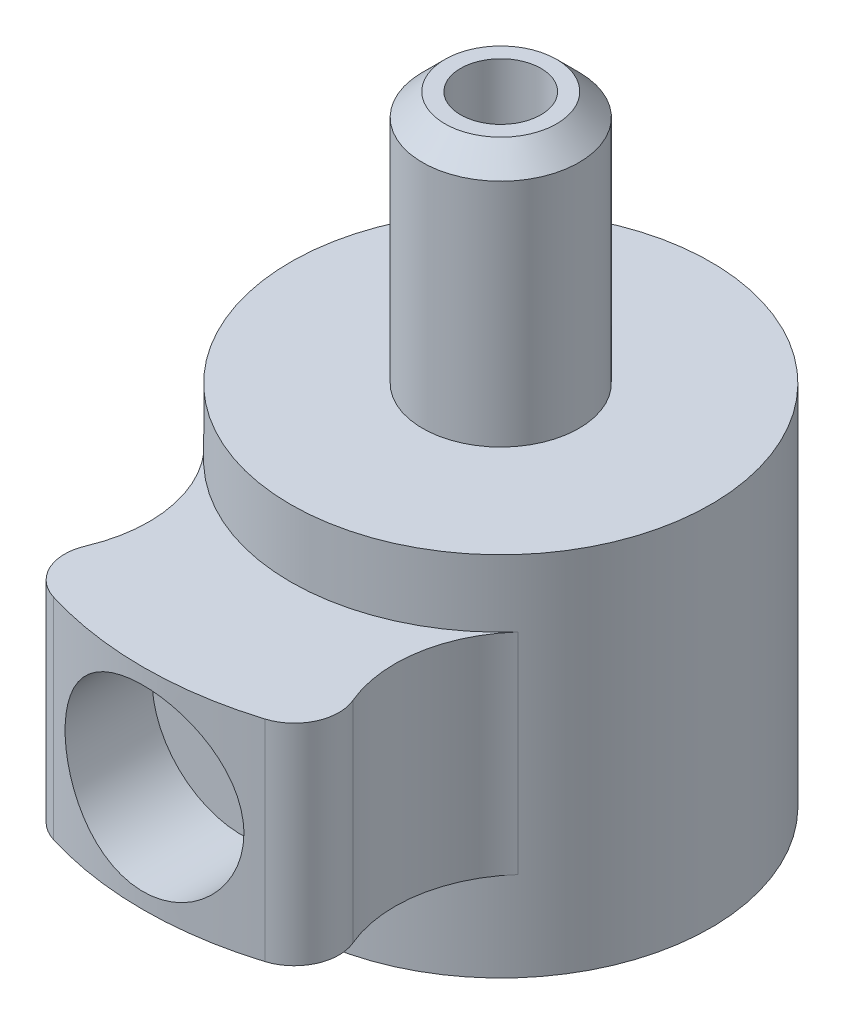
SolidWorks part; units mm, degrees
material "1060 Сплав"
ref_plane "Front Plane" through (0, 0, 0) normal (0, 0, 1) x (1, 0, 0)
ref_plane "Top Plane" through (0, 0, 0) normal (0, 1, 0) x (1, 0, 0)
ref_plane "Right Plane" through (0, 0, 0) normal (1, 0, 0) x (0, 0, -1)
sketch "Эскиз1" plane through (0, 0, 0) normal (1, 0, 0) x (0, 0, -1)
  line L0 (0, 0) -> (0, 10.689) construction
  line L1 (-3.4, 0) -> (-3.4, 6.5)
  line L2 (-3.4, 6.5) -> (-0.9, 6.5)
  line L3 (-0.9, 6.5) -> (-0.9, 13.85)
  line L4 (-0.9, 13.85) -> (-1.75, 13.85)
  line L5 (-1.75, 13.85) -> (-1.75, 8.2)
  line L6 (-1.75, 8.2) -> (-8, 8.2)
  line L7 (-8, 8.2) -> (-8, 0)
  line L8 (-8, 0) -> (-3.4, 0)
  line L9 (0, 0) -> (-3.4, 0) construction
  dimension "D1" = 6.8
  dimension "D2" = 1.8
  dimension "D3" = 3.5
  dimension "D4" = 16
  dimension "D5" = 8.2
  dimension "D6" = 13.85
  dimension "D7" = 6.5
revolve "Повернуть1" add sketch "Эскиз1" angle 360 about L0
sketch "Эскиз2" plane through (0, 8.2, 0) normal (0, 1, 0) x (1, 0, 0)
  line L0 (-5.75, -5.1213) -> (0, 0) construction
  line L1 (0, 0) -> (5.75, -5.1213) construction
  line L2 (-5.75, -5.1213) -> (5.75, -5.1213) construction
  line L3 (0, 0) -> (0, -5.1213) construction
  arc A0 (-5.75, -5.1213) -> (5.75, -5.1213) centre (0, 0) cw construction
  arc A1 (7.9903, -7.1166) -> (-7.9903, -7.1166) centre (0, 0) ccw
  arc A2 (3.5097, -3.126) -> (-3.5097, -3.126) centre (0, 0) ccw
  arc A3 (3.5097, -3.126) -> (7.9903, -7.1166) centre (5.75, -5.1213) ccw
  arc A4 (-7.9903, -7.1166) -> (-3.5097, -3.126) centre (-5.75, -5.1213) ccw
  point P4 (0, 7.7)
  dimension "D1" = 6
  dimension "D2" = 4.7
  dimension "D3" = 11.5
extrude "Вырез-Вытянуть1" cut sketch "Эскиз2" against normal through all
fillet "Скругление1" radius 1 2 edges at (3.5553, 4.1, 7.1666) (-3.5553, 4.1, 7.1666)
ref_plane "Плоскость1" through (0, 8.2, 8) normal (0, 0, 1) x (1, 0, 0)
sketch "Эскиз5" plane through (0, 8.2, 0) normal (0, 1, 0) x (1, 0, 0)
  circle A0 centre (0, 0) radius 4.7
extrude "Вырез-Вытянуть4" cut sketch "Эскиз5" against normal blind 1.5 flip side to cut
extrude "Вырез-Вытянуть5" cut sketch "Эскиз5<2>" along normal blind 2 from surface flip side to cut starting at face at (0, 0, -3.4)
sketch "Эскиз5<2>" plane through (0, 8.2, 0) normal (0, 1, 0) x (1, 0, 0) same geometry as "Эскиз5"
chamfer "Фаска1" distance 0.5 angle 45 1 edges at (0, 13.85, -1.75)
hole_wizard "M2 Tapped Hole1" positions "Sketch2" profile "Sketch3" tap size "M2" standard "ISO"
sketch "Sketch2" plane through (0, 8.2, 8) normal (0, 0, 1) x (1, 0, 0)
  line L0 (0, -3.85) -> (2.3648, -3.85)
  line L2 (2.3648, -6.2) -> (2.3648, -1.5) construction
  line L3 (0, -3.85) -> (0, -6.2)
  line L5 (-2.3648, -6.2) -> (2.3648, -6.2) construction
  point P0 (0, -3.85)
  point P8 (2.3648, -3.85)
  point P17 (0, -6.2)
sketch "Sketch3" plane through (0, 4.35, 8) normal (1, 0, 0) x (0, -1, 0)
  line L0 (0, 0) -> (0, 5.6807)
  line L1 (0, 5.6807) -> (0.8, 5.2)
  line L2 (0.8, 5.2) -> (0.8, 0)
  line L5 (0.8, 0) -> (0, 0)
  line L10 (0, 5.6807) -> (-0.8, 5.2) construction
  line L11 (0, -6.35) -> (0, 107.95) construction
  dimension "Tap Drill Dia." = 1.6
  dimension "Tap Drill Depth" = 5.2
  dimension "Drill Angle" = 118
cosmetic thread "Hole Thread1" parameters "D1"=4, "D2"=2
sketch "Sketch4" plane through (0, 8.2, 8) normal (0, 0, 1) x (1, 0, 0)
  circle A0 centre (0, -3.85) radius 2
  dimension "D1" = 4
extrude "Cut-Extrude1" cut sketch "Sketch4" against normal blind 2.2
